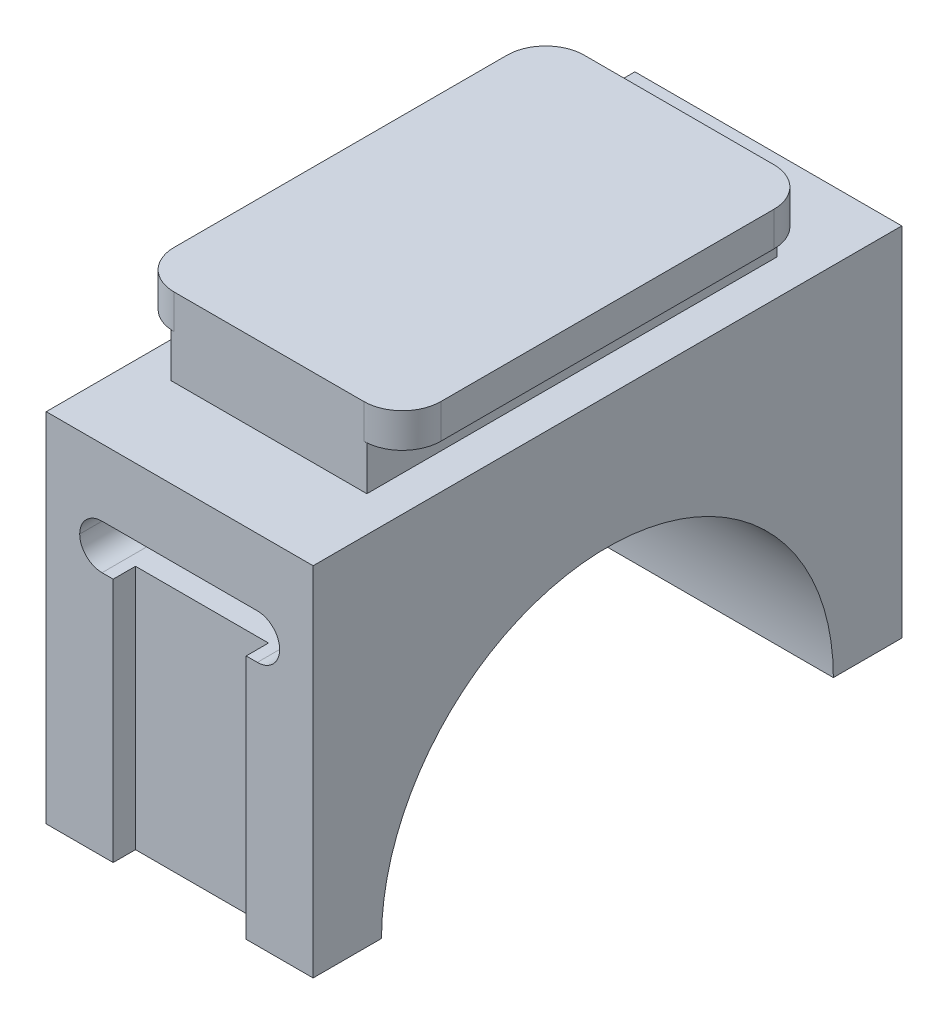
SolidWorks part; units mm, degrees
material "ABS"
ref_plane "Front Plane" through (0, 0, 0) normal (0, 0, 1) x (1, 0, 0)
ref_plane "Top Plane" through (0, 0, 0) normal (0, 1, 0) x (1, 0, 0)
ref_plane "Right Plane" through (0, 0, 0) normal (1, 0, 0) x (0, 0, -1)
sketch "Sketch1" plane through (0, 0, 0) normal (0, 1, 0) x (1, 0, 0)
  line L1 (2.1971, 0) -> (12.9921, 0)
  line L2 (0, -2.1971) -> (0, -21.1455)
  line L3 (2.1971, -23.3426) -> (12.9921, -23.3426)
  line L4 (15.1892, -2.1971) -> (15.1892, -21.1455)
  arc A0 (0, -21.1455) -> (2.1971, -23.3426) centre (2.1971, -21.1455) ccw
  arc A1 (12.9921, -23.3426) -> (15.1892, -21.1455) centre (12.9921, -21.1455) ccw
  arc A2 (12.9921, 0) -> (15.1892, -2.1971) centre (12.9921, -2.1971) cw
  arc A3 (2.1971, 0) -> (0, -2.1971) centre (2.1971, -2.1971) ccw
  point P7 (0, -23.3426)
  point P12 (15.1892, 0)
  point P15 (0, 0)
  dimension "D3" = 2.1971
  dimension "D1" = 15.1892
  dimension "D2" = 23.3426
extrude "Boss-Extrude1" add sketch "Sketch1" along normal blind 1.9558
sketch "Sketch2" plane through (0, 0, 0) normal (0, -1, 0) x (1, 0, 0)
  line L0 (12.9921, 0) -> (2.1971, 0) construction
  line L1 (13.1699, 0) -> (2.0193, 0)
  line L2 (13.1699, 0) -> (13.1699, 23.3426)
  line L3 (13.1699, 23.3426) -> (2.0193, 23.3426)
  line L4 (2.0193, 0) -> (2.0193, 23.3426)
  line L7 (2.1971, 23.3426) -> (12.9921, 23.3426) construction
  line L8 (0, 2.1971) -> (0, 21.1455) construction
  line L9 (15.1892, 21.1455) -> (15.1892, 2.1971) construction
  dimension "D1" = 2.0193
  dimension "D2" = 2.0193
extrude "Boss-Extrude2" add sketch "Sketch2" along normal blind 2.5019
sketch "Sketch3" plane through (0, -2.5019, 0) normal (0, -1, 0) x (1, 0, 0)
  line L0 (15.1892, 21.1455) -> (15.1892, 2.1971) construction
  line L1 (15.1892, -5.08) -> (0, -5.08)
  line L2 (15.1892, -5.08) -> (15.1892, 28.4226)
  line L3 (15.1892, 28.4226) -> (0, 28.4226)
  line L4 (0, -5.08) -> (0, 28.4226)
  line L5 (0, 2.1971) -> (0, 21.1455) construction
  line L6 (13.1699, 23.3426) -> (2.0193, 23.3426) construction
  line L7 (2.0193, 0) -> (13.1699, 0) construction
  dimension "D1" = 5.08
  dimension "D2" = 5.08
extrude "Boss-Extrude3" add sketch "Sketch3" along normal blind 20.32
sketch "Sketch4" plane through (15.1892, 0, 0) normal (1, 0, 0) x (0, 0, -1)
  line L0 (5.08, -22.8219) -> (-28.4226, -22.8219) construction
  circle A0 centre (-11.6713, -22.8219) radius 12.8587
  dimension "D1" = 25.7175
extrude "Cut-Extrude1" cut sketch "Sketch4" against normal through all
sketch "Sketch5" plane through (0, 0, 28.4226) normal (0, 0, 1) x (1, 0, 0)
  line L0 (15.1892, -2.5019) -> (0, -2.5019) construction
  line L1 (1.905, -6.3119) -> (13.2842, -6.3119)
  line L2 (1.905, -6.3119) -> (1.905, -8.8519)
  line L3 (1.905, -8.8519) -> (13.2842, -8.8519)
  line L4 (13.2842, -6.3119) -> (13.2842, -8.8519)
  line L5 (15.1892, -22.8219) -> (15.1892, -2.5019) construction
  line L6 (0, -22.8219) -> (0, -2.5019) construction
  dimension "D1" = 3.81
  dimension "D2" = 1.905
  dimension "D3" = 1.905
  dimension "D4" = 2.54
extrude "Cut-Extrude2" cut sketch "Sketch5" against normal through all
fillet "Fillet1" radius 1.27 4 edges at (13.2842, -8.8519, 11.6713) (13.2842, -6.3119, 11.6713) (1.905, -6.3119, 11.6713) (1.905, -8.8519, 11.6713)
sketch "Sketch6" plane through (0, 0, -5.08) normal (0, 0, -1) x (-1, 0, 0)
  line L0 (-3.175, -8.8519) -> (-12.0142, -8.8519) construction
  line L1 (-11.3792, -8.8519) -> (-3.81, -8.8519)
  line L2 (-11.3792, -8.8519) -> (-11.3792, -22.8219)
  line L3 (-11.3792, -22.8219) -> (-3.81, -22.8219)
  line L4 (-3.81, -8.8519) -> (-3.81, -22.8219)
  line L5 (0, -22.8219) -> (-15.1892, -22.8219) construction
  line L6 (0, -22.8219) -> (0, -2.5019) construction
  line L7 (-15.1892, -22.8219) -> (-15.1892, -2.5019) construction
  dimension "D1" = 3.81
  dimension "D2" = 3.81
extrude "Cut-Extrude3" cut sketch "Sketch6" against normal blind 1.27
sketch "Sketch7" plane through (0, 0, 28.4226) normal (0, 0, 1) x (1, 0, 0)
  line L0 (15.1892, -22.8219) -> (0, -22.8219) construction
  line L1 (11.3792, -22.8219) -> (3.81, -22.8219)
  line L2 (11.3792, -22.8219) -> (11.3792, -8.8519)
  line L3 (11.3792, -8.8519) -> (3.81, -8.8519)
  line L4 (3.81, -22.8219) -> (3.81, -8.8519)
  line L5 (3.175, -8.8519) -> (12.0142, -8.8519) construction
  line L6 (0, -22.8219) -> (0, -2.5019) construction
  line L7 (15.1892, -22.8219) -> (15.1892, -2.5019) construction
  dimension "D1" = 3.81
  dimension "D2" = 3.81
extrude "Cut-Extrude4" cut sketch "Sketch7" against normal blind 1.27
